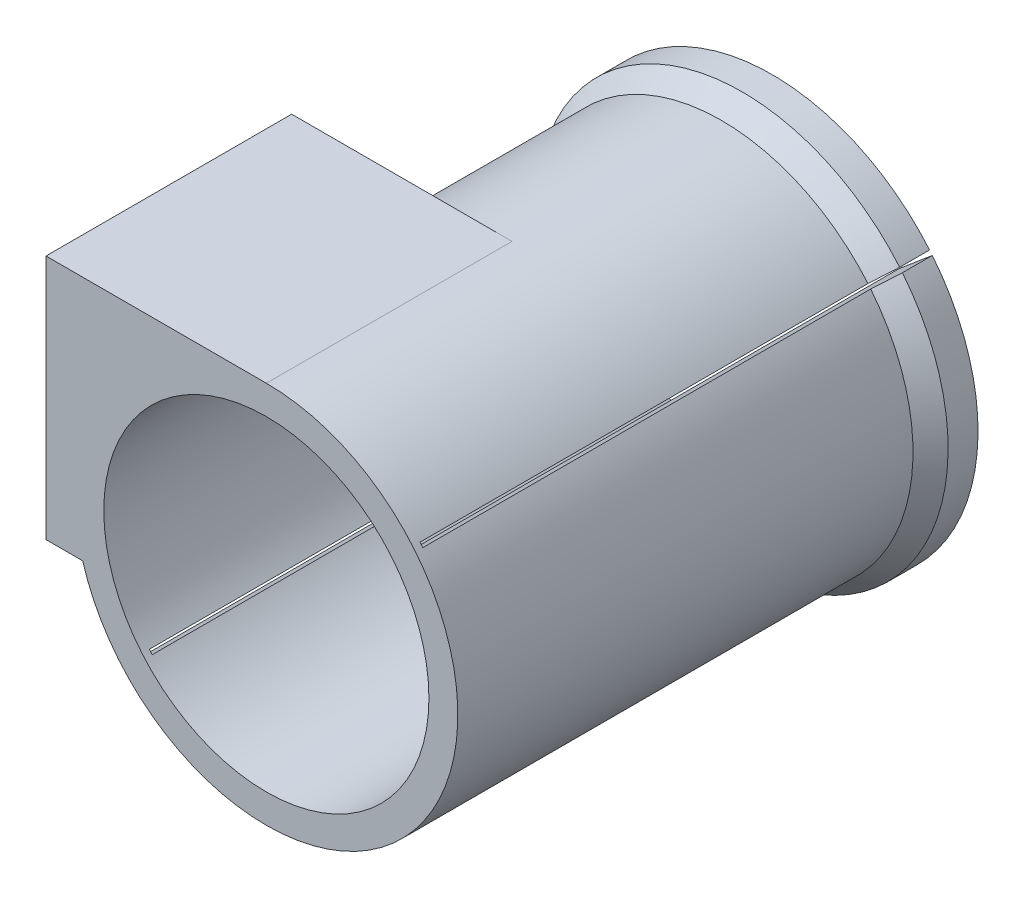
SolidWorks part; units mm, degrees
ref_plane "Alzado" through (0, 0, 0) normal (0, 0, 1) x (1, 0, 0)
ref_plane "Planta" through (0, 0, 0) normal (0, 1, 0) x (1, 0, 0)
ref_plane "Vista lateral" through (0, 0, 0) normal (1, 0, 0) x (0, 0, -1)
sketch "Croquis1" plane through (0, 0, 0) normal (0, 0, 1) x (1, 0, 0)
  circle A0 centre (0, 0) radius 11.25
  circle A1 centre (0, 0) radius 13.25
  dimension "D1" = 22.5
  dimension "D2" = 26.5
extrude "Saliente-Extruir1" add sketch "Croquis1" along normal blind 35
sketch "Croquis2" plane through (0, 0, 35) normal (0, 0, 1) x (1, 0, 0)
  line L0 (-13.25, 16.0125) -> (-13.25, -12.4319) construction
  line L1 (-15.25, 13.25) -> (0, 13.25)
  line L2 (-15.25, 13.25) -> (-15.25, -3.75)
  line L3 (-15.25, -3.75) -> (0, -3.75)
  line L4 (0, 13.25) -> (0, -3.75)
  circle A0 centre (0, 0) radius 13.25
  circle A1 centre (0, 0) radius 13.25 construction
  circle M7 centre (0, 0) radius 13.25
  dimension "D1" = 17
  dimension "D2" = 2
extrude "Saliente-Extruir2" add sketch "Croquis2" against normal blind 17 contours L1 L0 M7 | L0 L1 L2 L3 | A0 L0 L3 region at (-10.2904, 10.2904, 35) region at (-14.25, 4.75, 35) region at (-13.0881, -2.8164, 35)
sketch "Croquis3" plane through (0, 0, 0) normal (0, 0, -1) x (-1, 0, 0)
  circle A0 centre (0, 0) radius 13.25
  circle A1 centre (0, 0) radius 14.25
  dimension "D1" = 28.5
extrude "Saliente-Extruir3" add sketch "Croquis3" against normal blind 2
sketch "Croquis4" plane through (0, 0, 35) normal (0, 0, 1) x (1, 0, 0)
  line L0 (-20.9303, -17.6381) -> (20.9303, 17.6381)
  line L1 (20.9303, 17.6381) -> (21.1237, 17.4087)
  line L2 (21.1237, 17.4087) -> (-20.737, -17.8675)
  line L3 (-20.737, -17.8675) -> (-20.9303, -17.6381)
  point P2 (19.3765, 12.1475)
  point P5 (-21.8399, -18.9941)
  point P6 (0, 0)
  point P7 (-25.7072, -81.0547)
  point P8 (0, 0)
  point P10 (20.9303, 17.6381)
  dimension "D1" = 0.3
extrude "Cortar-Extruir1" cut sketch "Croquis4" against normal up to surface (35 mm away) from offset 0.5 up to face at (11.25, 0, 0) offset against normal yes
chamfer "Chaflán2" distance 1.5 angle 35 2 edges at (-8.5384, 10.1321, 2) (8.5384, -10.1321, 2) first distance on face at (0.0725, -0.086, 18.25)
